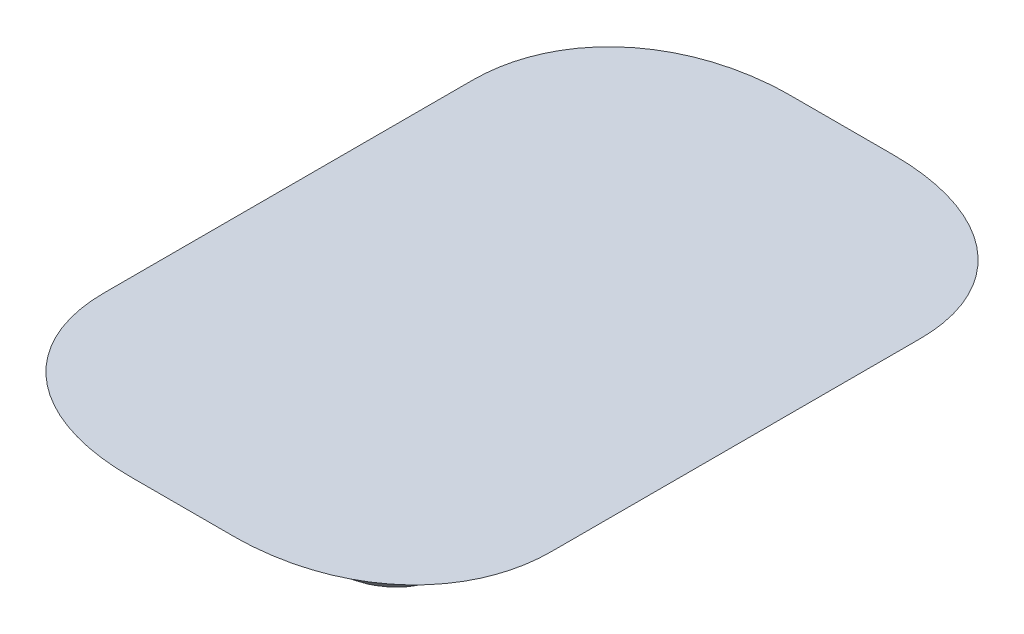
SolidWorks part; units mm, degrees
ref_plane "Plane1" through (0, 0, 0) normal (0, 0, 1) x (1, 0, 0)
ref_plane "Plane2" through (0, 0, 0) normal (0, 1, 0) x (1, 0, 0)
ref_plane "Plane3" through (0, 0, 0) normal (1, 0, 0) x (0, 0, -1)
sketch "Sketch1" plane through (0, 0, 0) normal (0, 0, 1) x (1, 0, 0)
  line L0 (-25, 1) -> (25, 1)
  line L1 (-25, 1) -> (-25, 0)
  line L2 (25, 0) -> (-25, 0)
  line L3 (25, 0) -> (25, 1)
  line L4 (0, 1) -> (0, 0) construction
  line L5 (50, 0) -> (-50, 0) construction
  dimension "D1" = 50
  dimension "D2" = 1
extrude "Base-Extrude" add sketch "Sketch1" along normal mid plane 50
sketch "Sketch2" plane through (0, 0, 0) normal (0, 0, 1) x (1, 0, 0)
  line L0 (0, 0) -> (0, -11.1464) construction
  line L1 (-10, 0) -> (-4.9654, -6)
  line L2 (25, 0) -> (-25, 0) construction
  line L3 (-4.9654, -6) -> (4.9654, -6)
  line L4 (-10, 0) -> (10, 0)
  line L5 (10, 0) -> (4.9654, -6)
  point P9 (0, 0)
  dimension "D1" = 20
  dimension "D2" = 50
  dimension "D3" = 6
extrude "Boss-Extrude1" add sketch "Sketch2" along normal mid plane 30
draft "Draft1" type of draft neutral plane draft angle 25 faces to draft 2 face at (0, -3, 15) face at (0, -3, -15) neutral plane through (25, 0, 25) neutral plane normal (0, -1, 0) parameters "D1"=25
fillet "Fillet2" radius 5 12 edges at (0, 0, 15) (10, 0, 0) (-7.4827, -3, -13.6011) (-10, 0, 0) (0, -6, -12.2022) (-4.9654, -6, 0) (7.4827, -3, 13.6011) (4.9654, -6, 0) (-7.4827, -3, 13.6011) (0, -6, 12.2022) (0, 0, -15) (7.4827, -3, -13.6011)
sketch "Sketch3" plane through (25, 0, 0) normal (1, 0, 0) x (0, 0, -1)
  line L4 (25, 1) -> (-25, 1)
  line L5 (-25, 1) -> (-25, 0)
  line L6 (-25, 0) -> (25, 0)
  line L7 (25, 0) -> (25, 1)
  line L8 (25, 1) -> (-25, 1)
  line L9 (-25, 1) -> (-25, 0)
  line L10 (-25, 0) -> (25, 0)
  line L11 (25, 0) -> (25, 1)
  dimension "D1" = 0
extrude "Cut-Extrude1" cut sketch "Sketch3" against normal through all
sketch "Orientation sketch" plane through (0, 0, 0) normal (0, 1, 0) x (-1, 0, 0)
  line L4 (12.3315, -10.1489) -> (12.3315, 10.1489)
  line L5 (2.8237, 18.1854) -> (-2.8237, 18.1854)
  line L6 (-12.3315, 10.1489) -> (-12.3315, -10.1489)
  line L7 (-2.8237, -18.1854) -> (2.8237, -18.1854)
  line L8 (12.3315, -10.1489) -> (12.3315, 10.1489)
  line L9 (2.8237, 18.1854) -> (-2.8237, 18.1854)
  line L10 (-12.3315, 10.1489) -> (-12.3315, -10.1489)
  line L11 (-2.8237, -18.1854) -> (2.8237, -18.1854)
  ellipse E4 centre (-0.7225, -7.1516) end of major axis (11.3941, -13.8851) minor radius 10 (2.8237, -18.1854) -> (12.3315, -10.1489) ccw
  ellipse E5 centre (-0.7225, 7.1516) end of major axis (11.3941, 13.8851) minor radius 10 (12.3315, 10.1489) -> (2.8237, 18.1854) ccw
  ellipse E6 centre (0.7225, 7.1516) end of major axis (12.8392, 0.4181) minor radius 10 (-2.8237, 18.1854) -> (-12.3315, 10.1489) ccw
  ellipse E7 centre (0.7225, -7.1516) end of major axis (12.8392, -0.4181) minor radius 10 (-12.3315, -10.1489) -> (-2.8237, -18.1854) ccw
  ellipse E8 centre (-0.7225, -7.1516) end of major axis (11.3941, -13.8851) minor radius 10 (2.8237, -18.1854) -> (12.3315, -10.1489) ccw
  ellipse E9 centre (-0.7225, 7.1516) end of major axis (11.3941, 13.8851) minor radius 10 (12.3315, 10.1489) -> (2.8237, 18.1854) ccw
  ellipse E10 centre (0.7225, 7.1516) end of major axis (12.8392, 0.4181) minor radius 10 (-2.8237, 18.1854) -> (-12.3315, 10.1489) ccw
  ellipse E11 centre (0.7225, -7.1516) end of major axis (12.8392, -0.4181) minor radius 10 (-12.3315, -10.1489) -> (-2.8237, -18.1854) ccw
  dimension "D1" = 0
